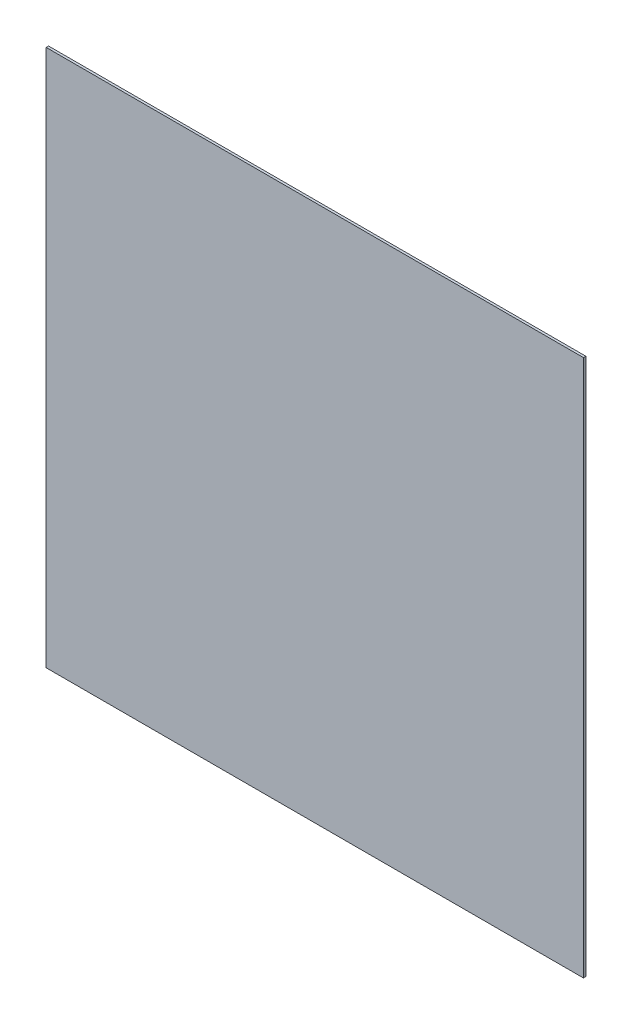
SolidWorks part; units mm, degrees
note: '?' marks a value the reader was unsure of.
ref_plane "Plan de face" through (0, 0, 0) normal (0, 0, 1) x (1, 0, 0)
ref_plane "Plan de dessus" through (0, 0, 0) normal (0, 1, 0) x (1, 0, 0)
ref_plane "Plan de droite" through (0, 0, 0) normal (1, 0, 0) x (0, 0, -1)
sketch "Esquisse1" plane through (0, 0, 0) normal (0, 0, 1) x (1, 0, 0)
  line L0 (31.2, -176.5) -> (-45, -176.5) construction
  line L1 (0, 0) -> (1066.8, 0)
  line L2 (0, 0) -> (0, -1066.8)
  line L4 (1066.8, 0) -> (1066.8, -1066.8)
  line L6 (0, -533.4) -> (1041.4, -533.4) construction
  line L8 (1047.9, 0) -> (1047.9, -1066.8) construction
  line L9 (31.2, -138.4) -> (-45, -138.4) construction
  line L11 (-45, -138.4) -> (-45, -214.6) construction
  line L12 (-45, -214.6) -> (31.2, -214.6) construction
  line L13 (31.2, -214.6) -> (31.2, -138.4) construction
  line L18 (21.675, -176.5) -> (21.675, -533.4) construction
  line L20 (21.675, -354.95) -> (156.4878, -354.95) construction
  line L52 (0, -1066.8) -> (1066.8, -1066.8)
  circle A6 centre (1047.9, -533.4) radius 5 construction
  circle A9 centre (21.675, -176.5) radius 3.175 construction
  circle A10 centre (15.32, -147.93) radius 3.175 construction
  circle A11 centre (15.32, -205.07) radius 3.175 construction
  circle A12 centre (15.32, -861.73) radius 3.175 construction
  circle A13 centre (21.675, -890.3) radius 3.175 construction
  circle A14 centre (15.32, -918.87) radius 3.175 construction
  circle A18 centre (15.32, -504.83) radius 3.175 construction
  circle A19 centre (21.675, -533.4) radius 3.175 construction
  circle A20 centre (15.32, -561.97) radius 3.175 construction
  circle A21 centre (1047.9, -133.4) radius 5 construction
  circle A22 centre (1047.9, -933.4) radius 5 construction
  point P41 (86, 11.6)
  point P44 (-4, -78.4)
  point P46 (86, -33.4)
  point P48 (-2.6584, -81.0833)
  point P49 (89, -35.2541)
  point P50 (89, 11.6)
  point P65 (-49, -982.8)
  point P66 (-3.2186, -982.8)
  point P67 (84, -1031.5398)
  point P68 (84, -1078.3)
  dimension "D3" = 6.35
  dimension "D4" = 138.4
  dimension "D5" = 76.2
  dimension "D6" = 45
  dimension "D7" = 76.2
  dimension "D8" = 9.525
  dimension "D9" = 6.35
  dimension "D11" = 10
  dimension "D13" = 9.53
  dimension "D14" = 15.88
  dimension "D16" = 2
  dimension "D1" = 1066.8
  dimension "D2" = 1066.8
  dimension "D10" = 18.9
  dimension "D15" = 356.9
  dimension "D12" = 533.4
extrude "Boss.-Extru.1" add sketch "Esquisse1" along normal blind 4.7625
fillet "Congé1" [suppressed] radius 30?
